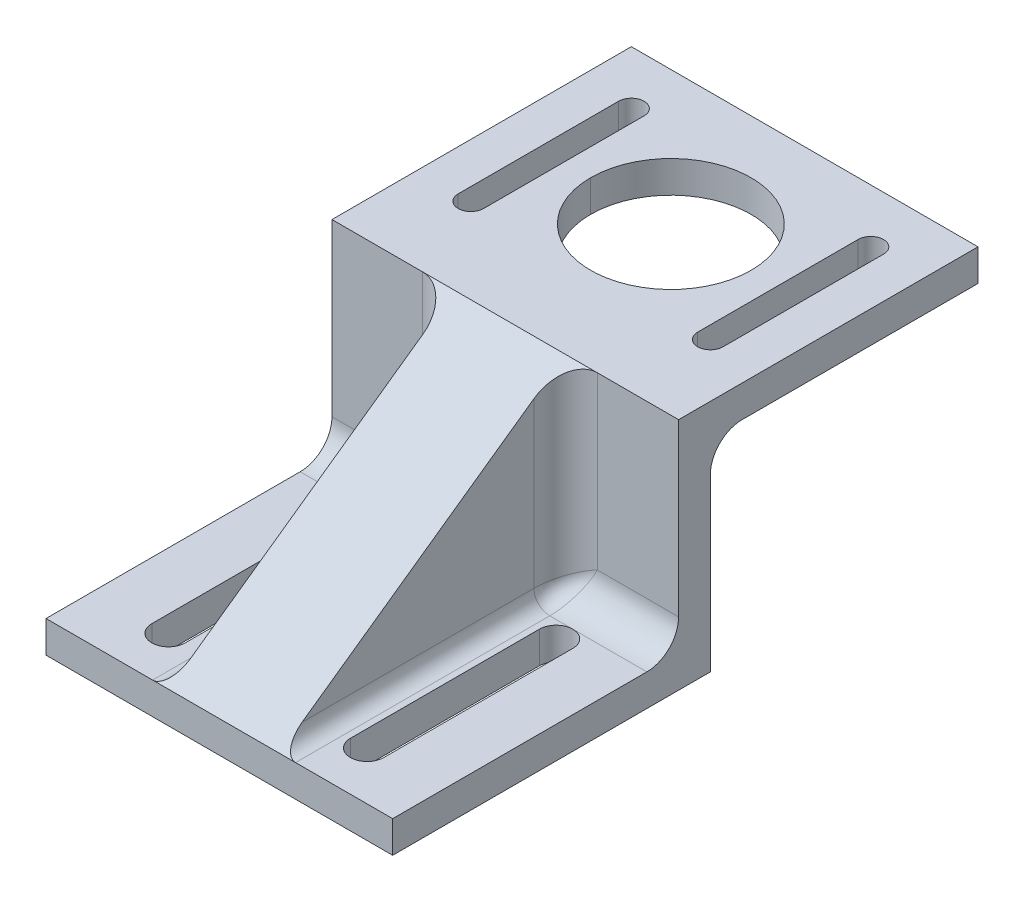
SolidWorks part; units mm, degrees
ref_plane "Front Plane" through (0, 0, 0) normal (0, 0, 1) x (1, 0, 0)
ref_plane "Top Plane" through (0, 0, 0) normal (0, 1, 0) x (1, 0, 0)
ref_plane "Right Plane" through (0, 0, 0) normal (1, 0, 0) x (0, 0, -1)
sketch "Sketch1" plane through (0, 0, 0) normal (0, 1, 0) x (1, 0, 0)
  line L0 (0, 0) -> (0, 0.001) construction
  line L1 (-10.1, 0) -> (-10.1, 0.001)
  line L2 (10.1, 0) -> (10.1, 0.001)
  line L3 (-15.075, -10.1) -> (-15.075, 10.101) construction
  line L4 (-21.8209, 16.8469) -> (21.8209, 16.8469)
  line L5 (-21.8209, 16.8469) -> (-21.8209, -16.8459)
  line L6 (-21.8209, -16.8459) -> (21.8209, -16.8459)
  line L7 (21.8209, 16.8469) -> (21.8209, -16.8459)
  line L8 (-16.675, -10.1) -> (-16.675, 10.101)
  line L9 (-13.475, -10.1) -> (-13.475, 10.101)
  line L10 (15.075, -10.1) -> (15.075, 10.101) construction
  line L11 (13.475, -10.1) -> (13.475, 10.101)
  line L12 (16.675, -10.1) -> (16.675, 10.101)
  line L13 (-13.475, 0.0005) -> (-10.1, 0.0005) construction
  line L14 (13.475, 0.0005) -> (10.1, 0.0005) construction
  line L15 (-16.675, -10.1) -> (-13.475, -10.1) construction
  line L16 (13.475, -10.1) -> (16.675, -10.1) construction
  line L17 (-15.075, 11.701) -> (-15.075, 16.8469) construction
  line L18 (-15.075, -11.7) -> (-15.075, -16.8459) construction
  line L19 (-16.675, 0.0005) -> (-21.8209, 0.0005) construction
  line L20 (16.675, 0.0005) -> (21.8209, 0.0005) construction
  arc A0 (-10.1, 0) -> (10.1, 0) centre (0, 0) ccw
  arc A1 (10.1, 0.001) -> (-10.1, 0.001) centre (0, 0.001) ccw
  arc A2 (-16.675, -10.1) -> (-13.475, -10.1) centre (-15.075, -10.1) ccw
  arc A3 (-13.475, 10.101) -> (-16.675, 10.101) centre (-15.075, 10.101) ccw
  arc A4 (13.475, -10.1) -> (16.675, -10.1) centre (15.075, -10.1) ccw
  arc A5 (16.675, 10.101) -> (13.475, 10.101) centre (15.075, 10.101) ccw
  point P3 (0, 0.0005)
  point P14 (-15.075, 0.0005)
  point P19 (15.075, 0.0005)
  point P35 (0, 10.101)
  point P37 (0, -10.1)
  dimension "D1" = 0.001
  dimension "D2" = 10.1
  dimension "D3" = 30.15
  dimension "D4" = 3.2
  dimension "D5" = 5.1459
extrude "Boss-Extrude2" add sketch "Sketch1" along normal blind 4
sketch "Sketch2" plane through (0, 4, 0) normal (0, 1, 0) x (1, 0, 0)
  line L1 (-21.8209, -16.8459) -> (21.8209, -16.8459)
  line L2 (-21.8209, -16.8459) -> (-21.8209, -20.8459)
  line L3 (-21.8209, -20.8459) -> (21.8209, -20.8459)
  line L4 (21.8209, -16.8459) -> (21.8209, -20.8459)
  dimension "D1" = 4
extrude "Boss-Extrude3" add sketch "Sketch2" against normal blind 29.5
sketch "Sketch3" plane through (0, 0, 16.8459) normal (0, 0, -1) x (-1, 0, 0)
  line L0 (21.8209, -25.5) -> (21.8209, 0) construction
  line L1 (-21.8209, -25.5) -> (21.8209, -25.5)
  line L2 (-21.8209, -25.5) -> (-21.8209, -21.5)
  line L3 (-21.8209, -21.5) -> (21.8209, -21.5)
  line L4 (21.8209, -25.5) -> (21.8209, -21.5)
  dimension "D1" = 4
extrude "Boss-Extrude4" add sketch "Sketch3" against normal blind 40
sketch "Sketch4" plane through (0, -25.5, 0) normal (0, -1, 0) x (1, 0, 0)
  line L0 (-12.5, 50.7459) -> (-12.5, 26.9459) construction
  line L1 (-10.4, 50.7459) -> (-10.4, 26.9459)
  line L2 (-14.6, 50.7459) -> (-14.6, 26.9459)
  line L3 (12.5, 50.7459) -> (12.5, 26.9459) construction
  line L4 (14.6, 50.7459) -> (14.6, 26.9459)
  line L5 (10.4, 50.7459) -> (10.4, 26.9459)
  line L6 (-14.6, 50.7459) -> (-10.4, 50.7459) construction
  line L7 (10.4, 50.7459) -> (14.6, 50.7459) construction
  line L8 (-14.6, 38.8459) -> (-21.8209, 38.8459) construction
  line L9 (-21.8209, 56.8459) -> (-21.8209, 16.8459) construction
  line L10 (14.6, 38.8459) -> (21.8209, 38.8459) construction
  line L11 (21.8209, 16.8459) -> (21.8209, 56.8459) construction
  line L12 (12.5, 52.8459) -> (12.5, 56.8459)
  line L14 (12.5, 24.8459) -> (12.5, 20.8459) construction
  line L17 (21.8209, 56.8459) -> (-21.8209, 56.8459) construction
  line L19 (12.5, 20.8459) -> (12.5, 16.8459) construction
  line L20 (-21.8209, 16.8459) -> (21.8209, 16.8459) construction
  arc A0 (-10.4, 50.7459) -> (-14.6, 50.7459) centre (-12.5, 50.7459) ccw
  arc A1 (-14.6, 26.9459) -> (-10.4, 26.9459) centre (-12.5, 26.9459) ccw
  arc A2 (14.6, 50.7459) -> (10.4, 50.7459) centre (12.5, 50.7459) ccw
  arc A3 (10.4, 26.9459) -> (14.6, 26.9459) centre (12.5, 26.9459) ccw
  point P2 (-12.5, 38.8459)
  point P7 (12.5, 38.8459)
  dimension "D1" = 4.2
  dimension "D2" = 25
  dimension "D3" = 4
extrude "Cut-Extrude1" cut sketch "Sketch4" against normal up to surface (4 mm away) contours A3 L4 A2 L5 | L2 A1 L1 A0 region at (-12.5, -25.5, 38.8459) region at (12.5, -25.5, 38.8459) up to face at (0, -21.5, 38.8459)
sketch "Sketch5" plane through (-10.4, 0, 0) normal (-1, 0, 0) x (0, 0, 1)
  line L0 (20.8459, 4) -> (56.8459, -21.5)
  line L1 (56.8459, -21.5) -> (20.8459, -21.5)
  line L2 (20.8459, -21.5) -> (20.8459, 4)
  point P6 (56.8459, -21.5)
extrude "Boss-Extrude5" add sketch "Sketch5" against normal blind 14 from offset 4 offset against normal yes
fillet "Fillet1" radius 4 5 edges at (14.7105, -21.5, 20.8459) (-14.1105, -21.5, 20.8459) (0, 0, 16.8459) (7.6, -8.75, 20.8459) (-6.4, -8.75, 20.8459)
fillet "Fillet2" radius 2 4 edges at (8.7716, -20.3284, 22.0175) (-7.5716, -20.3284, 22.0175) (7.6, -21.5, 40.8459) (-6.4, -21.5, 40.8459)
